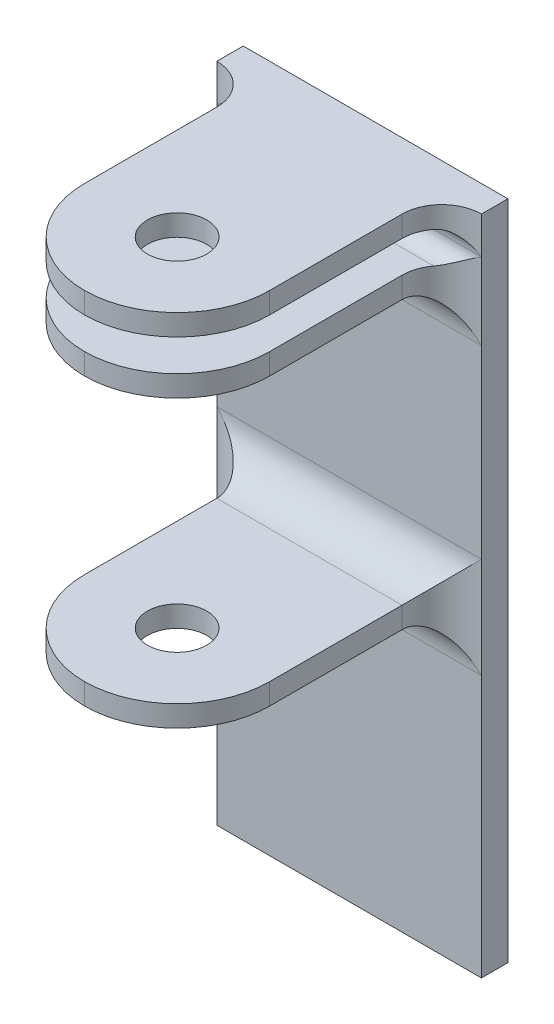
SolidWorks part; units mm, degrees
ref_plane "Plan de face" through (0, 0, 0) normal (1, 0, 0) x (0, 1, 0)
ref_plane "Plan de dessus" through (0, 0, 0) normal (0, 0, 1) x (0, 1, 0)
ref_plane "Plan de droite" through (0, 0, 0) normal (0, 1, 0) x (-1, 0, 0)
sketch "Esquisse1" plane through (0, 0, 0) normal (0, 0, 1) x (0, 1, 0)
  line L1 (0, 0) -> (250, 0)
  line L2 (0, 0) -> (0, 100)
  line L3 (0, 100) -> (250, 100)
  line L4 (250, 0) -> (250, 100)
  dimension "D1" = 250
  dimension "D2" = 100
extrude "Boss.-Extru.1" add sketch "Esquisse1" along normal blind 10
sketch "Esquisse2" plane through (0, 0, 10) normal (0, 0, 1) x (1, 0, 0)
  line L0 (-100, 250) -> (-100, 0) construction
  line L1 (-85, 230) -> (-15, 230)
  line L2 (-85, 230) -> (-85, 222)
  line L3 (-85, 222) -> (-15, 222)
  line L4 (-15, 230) -> (-15, 222)
  line L5 (-85, 250) -> (-15, 250)
  line L6 (0, 0) -> (0, 250) construction
  line L7 (0, 250) -> (-100, 250) construction
  line L8 (-85, 122) -> (-15, 122)
  line L9 (-85, 122) -> (-85, 114)
  line L10 (-85, 114) -> (-15, 114)
  line L11 (-15, 122) -> (-15, 114)
  line L12 (-85, 250) -> (-85, 242)
  line L13 (-85, 242) -> (-15, 242)
  line L14 (-15, 250) -> (-15, 242)
  dimension "D1" = 8
  dimension "D2" = 8
  dimension "D3" = 100
  dimension "D4" = 70
  dimension "D5" = 15
  dimension "D6" = 70
  dimension "D7" = 15
  dimension "D8" = 12
  dimension "D9" = 70
  dimension "D10" = 8
  dimension "D11" = 15
extrude "Boss.-Extru.2" add sketch "Esquisse2" along normal blind 100
fillet "Congé1" radius 35 6 edges at (-85, 226, 110) (-15, 226, 110) (-15, 118, 110) (-85, 118, 110) (-85, 246, 110) (-15, 246, 110)
sketch "Esquisse3" plane through (0, 250, 0) normal (0, 1, 0) x (-1, 0, 0)
  line L0 (0, 10) -> (0, 0) construction
  line L2 (0, 0) -> (100, 0) construction
  circle A0 centre (50, 75) radius 11.2
  point P5 (0, 0)
  point P6 (0, 0)
  dimension "D3" = 22.4
  dimension "D1" = 50
  dimension "D2" = 75
extrude "Enlèv. mat.-Extru.1" cut sketch "Esquisse3" against normal blind 150
fillet "Congé2" radius 15 9 edges at (-15, 118, 10) (-50, 122, 10) (-85, 118, 10) (-50, 114, 10) (-85, 246, 10) (-15, 246, 10) (-15, 226, 10) (-50, 222, 10) (-85, 226, 10)
fillet "Congé3" radius 6 2 edges at (-50, 242, 10) (-50, 230, 10)
